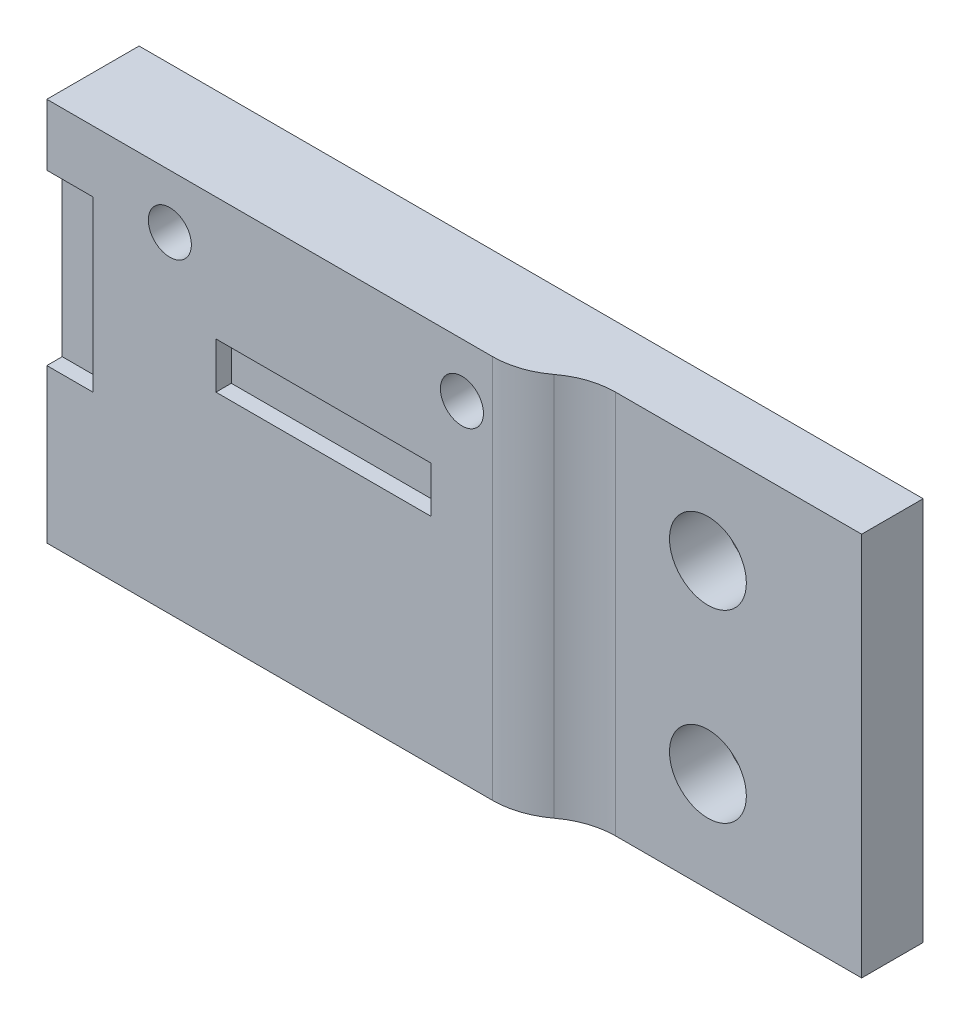
SolidWorks part; units mm, degrees
ref_plane "Front Plane" through (0, 0, 0) normal (0, 0, 1) x (1, 0, 0)
ref_plane "Top Plane" through (0, 0, 0) normal (0, 1, 0) x (1, 0, 0)
ref_plane "Right Plane" through (0, 0, 0) normal (1, 0, 0) x (0, 0, -1)
sketch "Sketch1" plane through (0, 0, 0) normal (0, 0, 1) x (1, 0, 0)
  line L1 (-20, -12.5) -> (20, -12.5)
  line L2 (-20, -12.5) -> (-20, 12.5)
  line L3 (-20, 12.5) -> (20, 12.5)
  line L4 (20, -12.5) -> (20, 12.5)
  line L5 (-20, -12.5) -> (20, 12.5) construction
  line L6 (-20, 12.5) -> (20, -12.5) construction
  point P0 (0, 0)
extrude "Boss-Extrude1" add sketch "Sketch1" along normal blind 6
sketch "Sketch3" plane through (0, 0, 0) normal (0, 0, 1) x (1, 0, 0)
  line L0 (20, 4.5) -> (0, 4.5) construction
  line L1 (20, -12.5) -> (20, 12.5) construction
  line L2 (20, 12.5) -> (20, 4.5) construction
  line L3 (20, 12.5) -> (-20, 12.5) construction
  line L4 (-20, 12.5) -> (-20, 8.5) construction
  line L5 (0, 4.5) -> (14, 4.5)
  line L6 (0, 4.5) -> (0, 1.5)
  line L7 (0, 1.5) -> (14, 1.5)
  line L8 (14, 4.5) -> (14, 1.5)
  line L9 (0, 4.5) -> (0, 12.5) construction
  line L10 (-20, 12.5) -> (-20, -12.5) construction
  line L11 (-20, 8.5) -> (-11, 8.5) construction
  line L12 (20, 12.5) -> (-20, 12.5) construction
  line L13 (-11, 8.5) -> (-8, 8.5)
  line L14 (-11, 8.5) -> (-11, -2.5)
  line L15 (-11, -2.5) -> (-8, -2.5)
  line L16 (-8, 8.5) -> (-8, -2.5)
extrude "Cut-Extrude1" cut sketch "Sketch3" against normal blind 1 from surface starting at face at (0, 0, 6)
sketch "Sketch4" plane through (0, 0, 0) normal (0, 0, 1) x (1, 0, 0)
  line L0 (20, 12.5) -> (16, 12.5) construction
  line L1 (20, 12.5) -> (-20, 12.5) construction
  line L2 (16, 12.5) -> (16, 9) construction
  line L3 (16, 9) -> (-3, 9) construction
  circle A0 centre (16, 9) radius 1.4
  circle A1 centre (-3, 9) radius 1.4
extrude "Cut-Extrude2" cut sketch "Sketch4" along normal blind 11
sketch "Sketch7" plane through (0, 0, 0) normal (0, 0, 1) x (1, 0, 0)
  line L0 (-20, -12.5) -> (20, -12.5) construction
  line L1 (-20, 12.5) -> (-11, 12.5)
  line L2 (-20, 12.5) -> (-20, -12.5)
  line L3 (-20, -12.5) -> (-11, -12.5)
  line L4 (-11, 12.5) -> (-11, -12.5)
extrude "Cut-Extrude5" cut sketch "Sketch7" along normal blind 21
sketch "Sketch8" plane through (0, 0, 0) normal (0, 0, 1) x (1, 0, 0)
  line L1 (20, 12.5) -> (40, 12.5)
  line L2 (20, 12.5) -> (20, -12.5)
  line L3 (20, -12.5) -> (40, -12.5)
  line L4 (40, 12.5) -> (40, -12.5)
extrude "Boss-Extrude2" add sketch "Sketch8" along normal blind 4
sketch "Sketch9" plane through (0, 0, 0) normal (0, 0, 1) x (1, 0, 0)
  line L0 (30, 6) -> (30, 12.5) construction
  line L1 (40, 12.5) -> (-11, 12.5) construction
  line L2 (30, -6) -> (30, -12.5) construction
  line L3 (-11, -12.5) -> (40, -12.5) construction
  circle A0 centre (30, 6) radius 2.5
  circle A1 centre (30, -6) radius 2.5
extrude "Cut-Extrude6" cut sketch "Sketch9" along normal through all
sketch "Sketch10" plane through (0, 0, 0) normal (0, 0, 1) x (1, 0, 0)
  line L2 (27.4521, -0.5678) -> (27.4521, 0.5678)
  line L3 (32.6259, 0.0583) -> (32.6259, -0.6051)
  line L4 (32.6259, 0.0583) -> (32.6259, 0.6051)
  arc A0 (32.6259, 0.6051) -> (27.4521, 0.5678) centre (30, 6) ccw
  arc A1 (27.4521, -0.5678) -> (32.6259, -0.6051) centre (30, -6) ccw
extrude "Cut-Extrude7" cut sketch "Sketch10" along normal blind 0.5
fillet "Fillet3" radius 1 4 edges at (27.4521, -0.5678, 0.25) (27.4521, 0.5678, 0.25) (32.6259, -0.6051, 0.25) (32.6259, 0.6051, 0.25)
fillet "Fillet4" radius 5 1 edges at (20, 0, 4)
fillet "Fillet5" radius 5 1 edges at (20, 0, 6)
